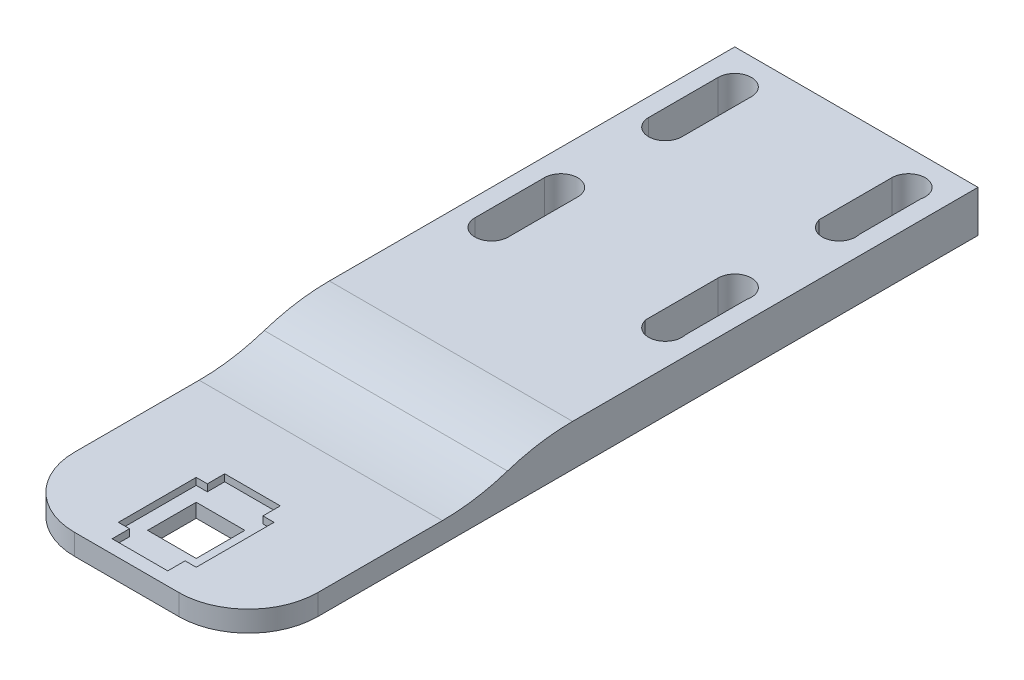
SolidWorks part; units mm, degrees
ref_plane "Front Plane" through (0, 0, 0) normal (0, 0, 1) x (1, 0, 0)
ref_plane "Top Plane" through (0, 0, 0) normal (0, 1, 0) x (1, 0, 0)
ref_plane "Right Plane" through (0, 0, 0) normal (1, 0, 0) x (0, 0, -1)
sketch "Sketch1" plane through (0, 0, 0) normal (0, 1, 0) x (1, 0, 0)
  line L1 (-17.3881, 19.9254) -> (17.6119, 19.9254)
  line L2 (-17.3881, 19.9254) -> (-17.3881, -85.0746)
  line L3 (-17.3881, -85.0746) -> (17.6119, -85.0746)
  line L4 (17.6119, 19.9254) -> (17.6119, -85.0746)
  dimension "D1" = 35
  dimension "D2" = 105
extrude "Boss-Extrude1" add sketch "Sketch1" along normal blind 6
sketch "Sketch2" plane through (0, 6, 0) normal (0, 1, 0) x (1, 0, 0)
  line L0 (17.6119, 19.9254) -> (-17.3881, 19.9254) construction
  line L1 (12.6119, -10.0746) -> (-12.3881, -10.0746)
  line L2 (12.6119, -10.0746) -> (12.6119, 14.9254)
  line L3 (12.6119, 14.9254) -> (-12.3881, 14.9254)
  line L4 (-12.3881, -10.0746) -> (-12.3881, 14.9254)
  line L5 (12.6119, -10.0746) -> (-12.3881, 14.9254) construction
  line L6 (12.6119, 14.9254) -> (-12.3881, -10.0746) construction
  point P0 (0.1119, 2.4254)
  point P7 (0.1119, 19.9254)
  dimension "D1" = 25
  dimension "D2" = 25
  dimension "D3" = 0
  dimension "D4" = 5
hole_wizard "M4 Clearance Hole1" positions "Sketch3" profile "Sketch4" hole size "M4" standard "ANSI Metric" end condition through all
sketch "Sketch3" plane through (0, 6, 0) normal (0, 1, 0) x (1, 0, 0)
  point P0 (-12.3881, 14.9254)
  point P3 (12.6119, 14.9254)
  point P6 (12.6119, -10.0746)
  point P9 (-12.3881, -10.0746)
sketch "Sketch4" plane through (-12.3881, 6, -14.9254) normal (1, 0, 0) x (0, 0, 1)
  line L0 (0, 0) -> (0, 6)
  line L1 (0, 6) -> (2.4, 6)
  line L2 (2.4, 6) -> (2.4, 0)
  line L5 (2.4, 0) -> (0, 0)
  line L11 (0, -6.35) -> (0, 107.95) construction
  dimension "Thru Hole Dia." = 4.8
  dimension "Thru Hole Depth" = 6
pattern_linear "LPattern2" count 2 spacing 10 along (0, 0, 1) of "M4 Clearance Hole1"
sketch "Sketch5" plane through (0, 6, 0) normal (0, 1, 0) x (1, 0, 0)
  line L1 (-14.7881, 14.9254) -> (-9.9881, 14.9254)
  line L2 (-14.7881, 14.9254) -> (-14.7881, 4.9254)
  line L3 (-14.7881, 4.9254) -> (-9.9881, 4.9254)
  line L4 (-9.9881, 14.9254) -> (-9.9881, 4.9254)
  line L5 (-14.7881, -10.0746) -> (-9.9881, -10.0746)
  line L6 (-14.7881, -10.0746) -> (-14.7881, -20.0746)
  line L7 (-14.7881, -20.0746) -> (-9.9881, -20.0746)
  line L8 (-9.9881, -10.0746) -> (-9.9881, -20.0746)
  line L9 (10.2119, 14.9254) -> (14.9426, 14.9254)
  line L10 (10.2119, 14.9254) -> (10.2119, 4.3527)
  line L11 (10.2119, 4.3527) -> (14.9426, 4.3527)
  line L12 (14.9426, 14.9254) -> (14.9426, 4.3527)
  line L13 (10.2119, -10.0746) -> (14.9426, -10.0746)
  line L14 (10.2119, -10.0746) -> (10.2119, -20.6473)
  line L15 (10.2119, -20.6473) -> (14.9426, -20.6473)
  line L16 (14.9426, -10.0746) -> (14.9426, -20.6473)
  circle A0 centre (-12.3881, 14.9254) radius 2.4 construction
  circle A1 centre (-12.3881, 4.9254) radius 2.4 construction
  circle A2 centre (-12.3881, -10.0746) radius 2.4 construction
  circle A3 centre (-12.3881, -20.0746) radius 2.4 construction
  circle A4 centre (12.6119, 14.9254) radius 2.4 construction
  circle A5 centre (12.6119, 4.9254) radius 2.4 construction
  circle A6 centre (12.6119, -10.0746) radius 2.4 construction
  circle A7 centre (12.6119, -20.0746) radius 2.4 construction
extrude "Cut-Extrude1" cut sketch "Sketch5" against normal through all
sketch "Sketch6" plane through (0, 6, 0) normal (0, 1, 0) x (1, 0, 0)
  line L1 (5.7119, -80.6746) -> (-5.4881, -80.6746)
  line L2 (5.7119, -80.6746) -> (5.7119, -69.4746)
  line L3 (5.7119, -69.4746) -> (-5.4881, -69.4746)
  line L4 (-5.4881, -80.6746) -> (-5.4881, -69.4746)
  line L5 (5.7119, -80.6746) -> (-5.4881, -69.4746) construction
  line L6 (5.7119, -69.4746) -> (-5.4881, -80.6746) construction
  line L9 (-17.3881, -85.0746) -> (17.6119, -85.0746) construction
  point P0 (0.1119, -75.0746)
  point P7 (0.1119, -85.0746)
  dimension "D1" = 11.2
  dimension "D2" = 11.2
  dimension "D3" = 10
  dimension "D4" = 0
extrude "Cut-Extrude2" cut sketch "Sketch6" against normal offset from surface (4 mm away) 2 up to face at (-12.3881, 0, 15.0746)
sketch "Sketch7" plane through (0, 2, 0) normal (0, 1, 0) x (1, 0, 0)
  line L0 (5.7119, -80.6746) -> (5.7119, -69.4746) construction
  line L1 (3.6119, -78.5746) -> (-3.3881, -78.5746)
  line L2 (3.6119, -78.5746) -> (3.6119, -71.5746)
  line L3 (3.6119, -71.5746) -> (-3.3881, -71.5746)
  line L4 (-3.3881, -78.5746) -> (-3.3881, -71.5746)
  line L5 (3.6119, -78.5746) -> (-3.3881, -71.5746) construction
  line L6 (3.6119, -71.5746) -> (-3.3881, -78.5746) construction
  line L7 (-17.3881, -85.0746) -> (17.6119, -85.0746) construction
  point P0 (0.1119, -75.0746)
  point P7 (5.7119, -75.0746)
  point P10 (0.1119, -85.0746)
  dimension "D1" = 0
  dimension "D2" = 0
  dimension "D3" = 7
  dimension "D4" = 7
extrude "Cut-Extrude3" cut sketch "Sketch7" against normal through all
sketch "Sketch8" plane through (0, 6, 0) normal (0, 1, 0) x (1, 0, 0)
  line L0 (5.7119, -69.4746) -> (-5.4881, -69.4746) construction
  line L1 (4.1119, -83.1746) -> (-3.8881, -83.1746)
  line L2 (4.1119, -83.1746) -> (4.1119, -66.9746)
  line L3 (4.1119, -66.9746) -> (-3.8881, -66.9746)
  line L4 (-3.8881, -83.1746) -> (-3.8881, -66.9746)
  line L5 (4.1119, -83.1746) -> (-3.8881, -66.9746) construction
  line L6 (4.1119, -66.9746) -> (-3.8881, -83.1746) construction
  line L7 (5.7119, -80.6746) -> (-5.4881, -80.6746) construction
  line L9 (3.6119, -71.5746) -> (-3.3881, -71.5746) construction
  point P0 (0.1119, -75.0746)
  point P11 (0.1119, -71.5746)
  dimension "D1" = 2.5
  dimension "D2" = 2.5
  dimension "D3" = 8
  dimension "D4" = 0
extrude "Cut-Extrude4" cut sketch "Sketch8" against normal up to surface (4 mm away) up to face at (0.1119, 2, 75.0746)
fillet "Fillet1" radius 10 2 edges at (17.6119, 3, 85.0746) (-17.3881, 3, 85.0746)
sketch "Sketch9" plane through (0, 0, 0) normal (0, -1, 0) x (1, 0, 0)
  line L0 (-17.3881, -19.9254) -> (-17.3881, 75.0746) construction
  line L1 (-17.3881, 44.0746) -> (19.6619, 44.0746)
  line L2 (-17.3881, 44.0746) -> (-17.3881, 85.0746)
  line L3 (-17.3881, 85.0746) -> (19.6619, 85.0746)
  line L4 (19.6619, 44.0746) -> (19.6619, 85.0746)
  line L5 (-7.3881, 85.0746) -> (7.6119, 85.0746) construction
  line L6 (5.7119, 69.4746) -> (4.1119, 69.4746) construction
  dimension "D1" = 25.4
  dimension "D2" = 0
extrude "Cut-Extrude5" cut sketch "Sketch9" along normal offset from surface (3 mm away) 3 from surface up to face at (0.1119, 0, 75.0746) starting at face at (0.1119, 6, 75.0746)
fillet "Fillet2" radius 30 1 edges at (0.1119, 3, 44.0746)
fillet "Fillet3" radius 30 1 edges at (0.1119, 6, 44.0746)
